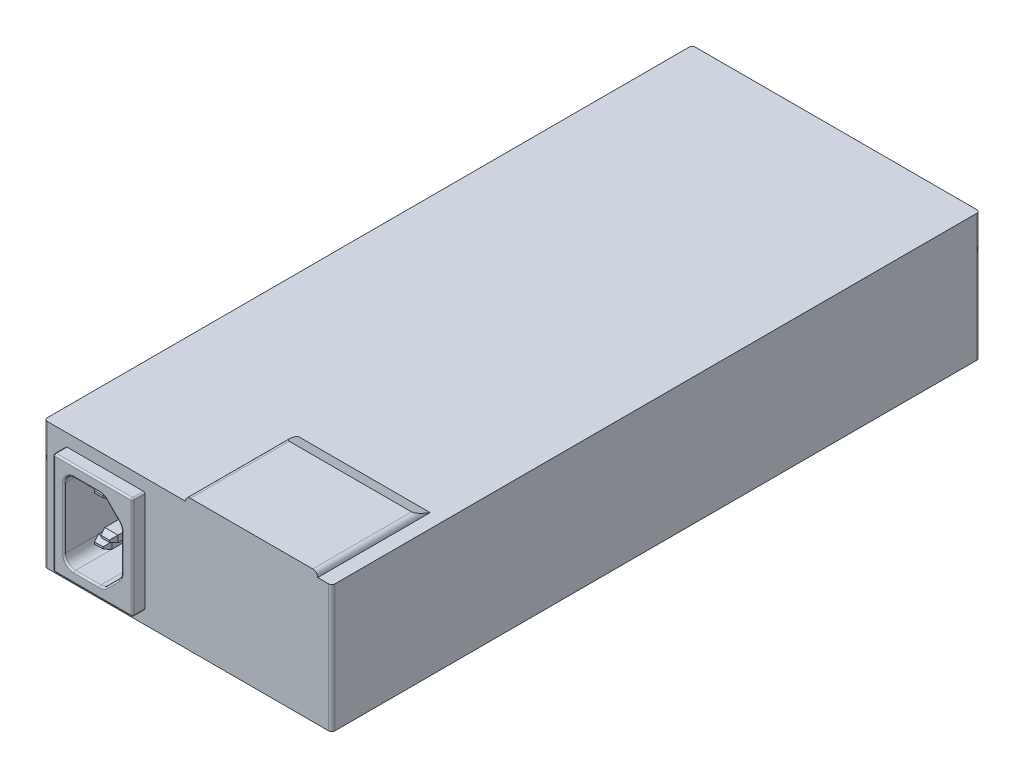
SolidWorks part; units mm, degrees
ref_plane "Front Plane" through (0, 0, 0) normal (0, 0, 1) x (1, 0, 0)
ref_plane "Top Plane" through (0, 0, 0) normal (0, 1, 0) x (1, 0, 0)
ref_plane "Right Plane" through (0, 0, 0) normal (1, 0, 0) x (0, 0, -1)
sketch "Sketch1" plane through (0, 0, 0) normal (0, 0, 1) x (1, 0, 0)
  line L0 (42.75, 40) -> (82.75, 40)
  line L1 (0, 0) -> (87, 0)
  line L2 (0, 0) -> (0, 38.5)
  line L3 (0, 38.5) -> (42.75, 38.5)
  line L4 (87, 0) -> (87, 38.5)
  line L8 (42.75, 38.5) -> (42.75, 40)
  line L9 (82.75, 40) -> (82.75, 38.5)
  line L10 (82.75, 38.5) -> (87, 38.5)
  dimension "D1" = 87
  dimension "D2" = 38.5
  dimension "D3" = 40
  dimension "D4" = 40
  dimension "D5" = 4.25
extrude "Boss-Extrude1" add sketch "Sketch1" against normal blind 34
sketch "Sketch2" plane through (0, 0, -34) normal (0, 0, -1) x (-1, 0, 0)
  line L0 (-42.75, 38.5) -> (0, 38.5) construction
  line L1 (0, 38.5) -> (-87, 38.5)
  line L2 (0, 38.5) -> (0, 0)
  line L3 (0, 0) -> (-87, 0)
  line L4 (-87, 38.5) -> (-87, 0)
  line L5 (0, 38.5) -> (0, 0) construction
extrude "Boss-Extrude2" add sketch "Sketch2" along normal blind 162
sketch "Sketch3" plane through (0, 0, -196) normal (0, 0, -1) x (-1, 0, 0)
  line L0 (-87, 0) -> (0, 0) construction
  line L1 (-75, 6) -> (-9.75, 6)
  line L2 (-75, 6) -> (-75, 4.35)
  line L3 (-75, 4.35) -> (-9.75, 4.35)
  line L4 (-9.75, 6) -> (-9.75, 4.35)
  line L5 (0, 0) -> (0, 38.5) construction
  line L6 (-87, 38.5) -> (-87, 0) construction
  dimension "D1" = 6
  dimension "D2" = 9.75
  dimension "D3" = 12
  dimension "D4" = 1.65
extrude "Boss-Extrude3" add sketch "Sketch3" along normal blind 8.86
fillet "Fillet1" radius 1 4 edges at (0, 19.25, -196) (87, 19.25, -196) (87, 19.25, 0) (0, 19.25, 0)
chamfer "Chamfer1" distance 1.5 angle 70 1 edges at (62.75, 40, -34) first distance on face at (62.75, 39.25, -34)
fillet "Fillet2" radius 1.5 2 edges at (42.75, 40, -14.9394) (82.75, 40, -14.9394)
sketch "Sketch4" plane through (0, 0, 0) normal (0, 0, 1) x (1, 0, 0)
  line L0 (18.5, 38.5) -> (18.5, 0) construction
  line L1 (6.5, 34.75) -> (30.5, 34.75)
  line L2 (6.5, 34.75) -> (6.5, 3.75)
  line L3 (6.5, 3.75) -> (30.5, 3.75)
  line L4 (30.5, 34.75) -> (30.5, 3.75)
  line L5 (6.5, 34.75) -> (30.5, 3.75) construction
  line L6 (6.5, 3.75) -> (30.5, 34.75) construction
  line L7 (42.75, 38.5) -> (1, 38.5) construction
  line L8 (1, 0) -> (86, 0) construction
  line L9 (0, 0) -> (0, 38.5) construction
  point P0 (18.5, 19.25)
  point P11 (18.5, 19.25)
  point P12 (0, 0)
  dimension "D1" = 31
  dimension "D2" = 24
  dimension "D3" = 6.5
extrude "Boss-Extrude4" add sketch "Sketch4" along normal blind 3.75
sketch "Sketch5" plane through (0, 0, 3.75) normal (0, 0, 1) x (1, 0, 0)
  line L0 (9.8, 19.25) -> (27.2, 19.25) construction
  line L1 (27.2, 13.7926) -> (27.2, 24.7074)
  line L2 (26.3213, 26.8287) -> (22.5787, 30.5713)
  line L3 (30.5, 3.75) -> (30.5, 34.75) construction
  line L4 (26.3213, 11.6713) -> (22.5787, 7.9287)
  line L14 (9.8, 7.05) -> (27.2, 7.05)
  line L15 (27.2, 7.05) -> (27.2, 31.45)
  line L16 (9.8, 31.45) -> (9.8, 7.05)
  line L17 (27.2, 31.45) -> (9.8, 31.45)
  line L18 (12.8, 7.05) -> (20.4574, 7.05)
  line L20 (9.8, 28.45) -> (9.8, 10.05)
  line L21 (20.4574, 31.45) -> (12.8, 31.45)
  arc A0 (12.8, 7.05) -> (9.8, 10.05) centre (12.8, 10.05) cw
  arc A1 (9.8, 28.45) -> (12.8, 31.45) centre (12.8, 28.45) cw
  arc A2 (22.5787, 7.9287) -> (20.4574, 7.05) centre (20.4574, 10.05) cw
  arc A3 (26.3213, 11.6713) -> (27.2, 13.7926) centre (24.2, 13.7926) ccw
  arc A4 (27.2, 24.7074) -> (26.3213, 26.8287) centre (24.2, 24.7074) ccw
  arc A5 (22.5787, 30.5713) -> (20.4574, 31.45) centre (20.4574, 28.45) ccw
  point P13 (0, 0)
  point P21 (21.7, 7.05)
  point P24 (27.2, 12.55)
  point P27 (27.2, 25.95)
  point P30 (21.7, 31.45)
  dimension "D2" = 3
  dimension "D6" = 3
  dimension "D3" = 45
  dimension "D4" = 3.3
  dimension "D5" = 5.5
  dimension "D1" = 3.3
extrude "Cut-Extrude1" cut sketch "Sketch5" against normal blind 16.75
sketch "Sketch6" plane through (0, 0, -13) normal (0, 0, 1) x (1, 0, 0)
  line L0 (15.3, 31.45) -> (15.3, 7.05) construction
  line L1 (20.4574, 31.45) -> (12.8, 31.45) construction
  line L2 (12.8, 7.05) -> (20.4574, 7.05) construction
  line L3 (9.8, 28.45) -> (9.8, 10.05) construction
  line L4 (13.3, 26.95) -> (17.3, 26.95)
  line L5 (13.3, 26.95) -> (13.3, 24.95)
  line L6 (13.3, 24.95) -> (17.3, 24.95)
  line L7 (17.3, 26.95) -> (17.3, 24.95)
  line L8 (13.3, 26.95) -> (17.3, 24.95) construction
  line L9 (13.3, 24.95) -> (17.3, 26.95) construction
  line L10 (13.3, 13.55) -> (17.3, 13.55)
  line L11 (13.3, 13.55) -> (13.3, 11.55)
  line L12 (13.3, 11.55) -> (17.3, 11.55)
  line L13 (17.3, 13.55) -> (17.3, 11.55)
  line L14 (13.3, 13.55) -> (17.3, 11.55) construction
  line L15 (13.3, 11.55) -> (17.3, 13.55) construction
  line L16 (20.4574, 31.45) -> (12.8, 31.45) construction
  line L17 (12.8, 7.05) -> (20.4574, 7.05) construction
  point P6 (15.3, 25.95)
  point P11 (15.3, 12.55)
  point P18 (17.3, 25.95)
  dimension "D1" = 5.5
  dimension "D2" = 2
  dimension "D3" = 4
  dimension "D4" = 5.5
  dimension "D5" = 5.5
extrude "Boss-Extrude5" add sketch "Sketch6" along normal offset from surface (11.75 mm away) 5 contours L7 L4 L5 L6 | L13 L10 L11 L12 region at (15.3, 25.95, -13) region at (15.3, 12.55, -13) up to face at (19.8057, 19.25, 3.75)
sketch "Sketch7" plane through (0, 0, -13) normal (0, 0, 1) x (1, 0, 0)
  line L0 (9.8, 19.25) -> (27.2, 19.25) construction
  line L1 (9.8, 28.45) -> (9.8, 10.05) construction
  line L2 (27.2, 13.7926) -> (27.2, 24.7074) construction
  line L3 (13.3, 26.95) -> (13.3, 24.95) construction
  line L4 (19.2, 20.25) -> (23.2, 20.25)
  line L5 (19.2, 20.25) -> (19.2, 18.25)
  line L6 (19.2, 18.25) -> (23.2, 18.25)
  line L7 (23.2, 20.25) -> (23.2, 18.25)
  line L8 (19.2, 20.25) -> (23.2, 18.25) construction
  line L9 (19.2, 18.25) -> (23.2, 20.25) construction
  line L10 (13.3, 26.95) -> (17.3, 26.95) construction
  line L11 (27.2, 13.7926) -> (27.2, 24.7074) construction
  point P6 (21.2, 19.25)
  dimension "D1" = 4
extrude "Boss-Extrude6" add sketch "Sketch7" along normal offset from surface (15.75 mm away) 1 up to face at (19.8057, 19.25, 3.75)
chamfer "Chamfer2" distance 0.7 angle 70 12 edges at (17.3, 12.55, -1.25) (15.3, 13.55, -1.25) (13.3, 12.55, -1.25) (15.3, 11.55, -1.25) (15.3, 24.95, -1.25) (13.3, 25.95, -1.25) (15.3, 26.95, -1.25) (17.3, 25.95, -1.25) (23.2, 19.25, 2.75) (21.2, 20.25, 2.75) (19.2, 19.25, 2.75) (21.2, 18.25, 2.75) first distance on face at (15.3, 12.55, -1.25) first distance on face at (15.3, 25.95, -1.25) first distance on face at (21.2, 19.25, 2.75)
fillet "Fillet3" radius 0.5 20 edges at (18.5, 3.75, 3.75) (6.5, 19.25, 3.75) (18.5, 34.75, 3.75) (30.5, 19.25, 3.75) (16.6287, 7.05, 3.75) (21.6054, 7.2784, 3.75) (24.45, 9.8, 3.75) (26.9716, 12.6446, 3.75) (27.2, 19.25, 3.75) (26.9716, 25.8554, 3.75) (24.45, 28.7, 3.75) (21.6054, 31.2216, 3.75) (16.6287, 31.45, 3.75) (10.6787, 30.5713, 3.75) (9.8, 19.25, 3.75) (10.6787, 7.9287, 3.75) (6.5, 3.75, 1.875) (30.5, 3.75, 1.875) (30.5, 34.75, 1.875) (6.5, 34.75, 1.875)
